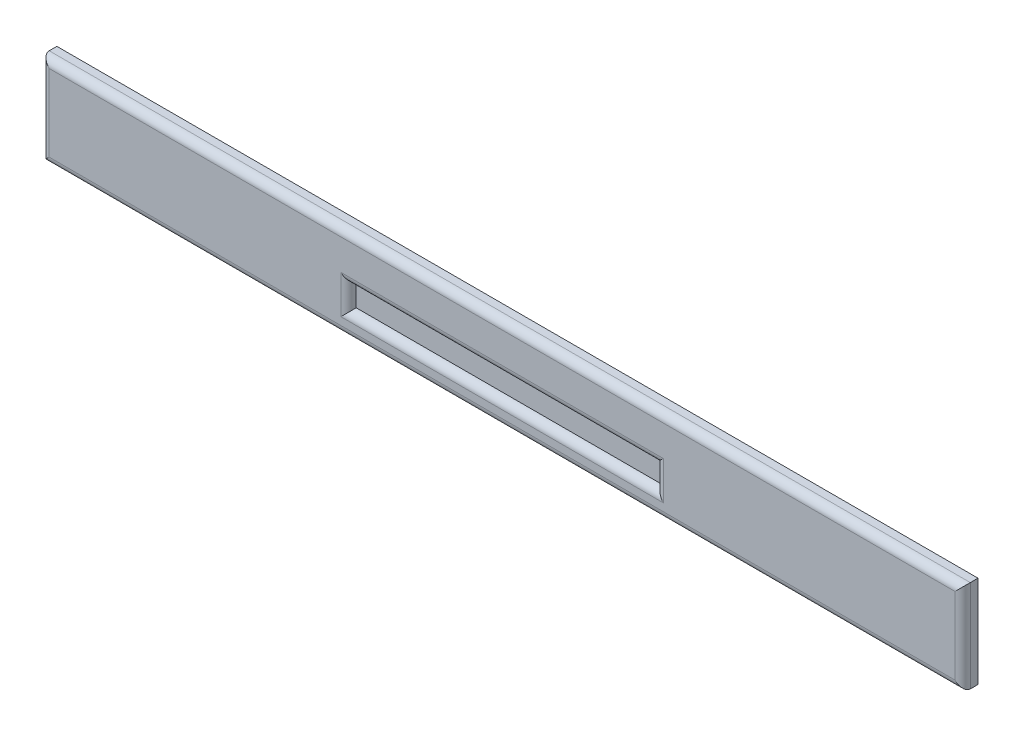
SolidWorks part; units mm, degrees
ref_plane "Front Plane" through (0, 0, 0) normal (0, 0, 1) x (1, 0, 0)
ref_plane "Top Plane" through (0, 0, 0) normal (0, 1, 0) x (1, 0, 0)
ref_plane "Right Plane" through (0, 0, 0) normal (1, 0, 0) x (0, 0, -1)
sketch "Sketch1" plane through (0, 0, 0) normal (0, 0, 1) x (1, 0, 0)
  line L1 (0, 0) -> (-6000, 0)
  line L2 (0, 0) -> (0, 600)
  line L3 (0, 600) -> (-6000, 600)
  line L4 (-6000, 0) -> (-6000, 600)
  dimension "D1" = 6000
  dimension "D2" = 600
extrude "Boss-Extrude1" add sketch "Sketch1" along normal blind 100
sketch "Sketch2" plane through (0, 0, 100) normal (0, 0, 1) x (1, 0, 0)
  line L0 (-6000, 0) -> (0, 0) construction
  line L1 (-4000, 150) -> (-2000, 150)
  line L2 (-4000, 150) -> (-4000, 300)
  line L3 (-4000, 300) -> (-2000, 300)
  line L4 (-2000, 150) -> (-2000, 300)
  line L5 (-4000, 150) -> (-2000, 300) construction
  line L6 (-4000, 300) -> (-2000, 150) construction
  point P0 (-3000, 225)
  point P9 (-3000, 0)
  dimension "D1" = 150
  dimension "D2" = 2000
  dimension "D3" = 150
extrude "Cut-Extrude1" cut sketch "Sketch2" against normal blind 50
fillet "Fillet2" radius 50 8 edges at (-3000, 0, 100) (-6000, 300, 100) (-3000, 600, 100) (0, 300, 100) (-3000, 300, 100) (-4000, 225, 100) (-3000, 150, 100) (-2000, 225, 100)
